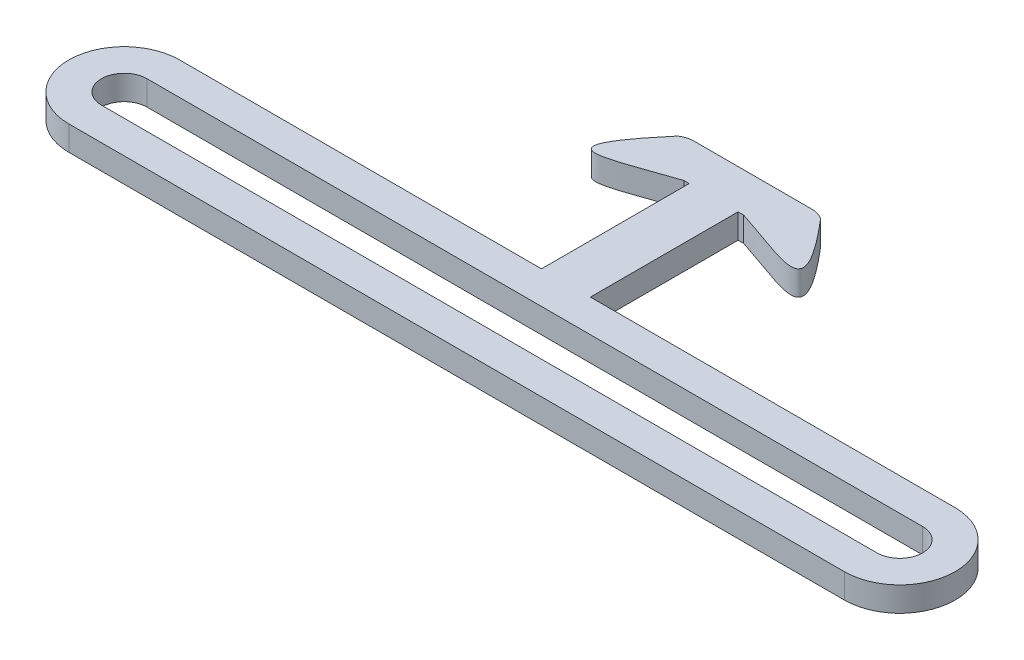
SolidWorks part; units mm, degrees
material "1060 Alloy"
ref_plane "Front Plane" through (0, 0, 0) normal (0, 0, 1) x (1, 0, 0)
ref_plane "Top Plane" through (0, 0, 0) normal (0, 1, 0) x (1, 0, 0)
ref_plane "Right Plane" through (0, 0, 0) normal (1, 0, 0) x (0, 0, -1)
sketch "Sketch1" plane through (0, 0, 0) normal (0, 1, 0) x (1, 0, 0)
  line L0 (-31.8944, 13.0361) -> (48.1635, 13.0361) construction
  line L5 (-31.8944, 18.7547) -> (5.4578, 18.7547)
  line L6 (-31.8944, 7.3176) -> (48.1635, 7.3176)
  line L7 (-31.8944, 13.0361) -> (48.1635, 13.0361) construction
  line L8 (-31.8944, 15.3938) -> (48.1635, 15.3938)
  line L9 (-31.8944, 10.6785) -> (48.1635, 10.6785)
  line L10 (10.5078, 18.7547) -> (48.1635, 18.7547)
  line L12 (5.4578, 18.7547) -> (5.4578, 34.0009)
  line L14 (10.5078, 18.7547) -> (10.5078, 34.0009)
  line L15 (1.9247, 38.047) -> (14.0602, 38.047)
  line L19 (10.5078, 34.0009) -> (11.0867, 34.0009)
  line L24 (4.9016, 34.0009) -> (5.4578, 34.0009)
  arc A0 (-31.8944, 18.7547) -> (-31.8944, 7.3176) centre (-31.8944, 13.0361) ccw
  arc A1 (48.1635, 7.3176) -> (48.1635, 18.7547) centre (48.1635, 13.0361) ccw
  arc A2 (-31.8944, 15.3938) -> (-31.8944, 10.6785) centre (-31.8944, 13.0361) ccw
  arc A3 (48.1635, 10.6785) -> (48.1635, 15.3938) centre (48.1635, 13.0361) ccw
  arc A4 (14.0602, 38.047) -> (15.372, 37.6535) centre (14.0602, 35.664) cw
  arc A5 (1.9247, 38.047) -> (0.6129, 37.6535) centre (1.9247, 35.664) ccw
  spline S0 degree 3 poles (0.6129, 37.6535) (-5.8846, 30.0339) (-1.4438, 31.8045) (4.1584, 33.7664) (4.9016, 34.0009) knots 0 0 0 0 0.594261 0.687272 0.687272 0.687272 0.687272
  spline S1 degree 3 poles (15.372, 37.6535) (21.9349, 29.9571) (17.4561, 31.7844) (11.8255, 33.7667) (11.0867, 34.0009) knots 0 0 0 0 0.596031 0.688115 0.688115 0.688115 0.688115
  point P2 (8.1345, 13.0361)
  point P4 (8.1345, 13.0361)
  dimension "D1" = 80.0579
extrude "Boss-Extrude3" add sketch "Sketch1" along normal blind 2.54
